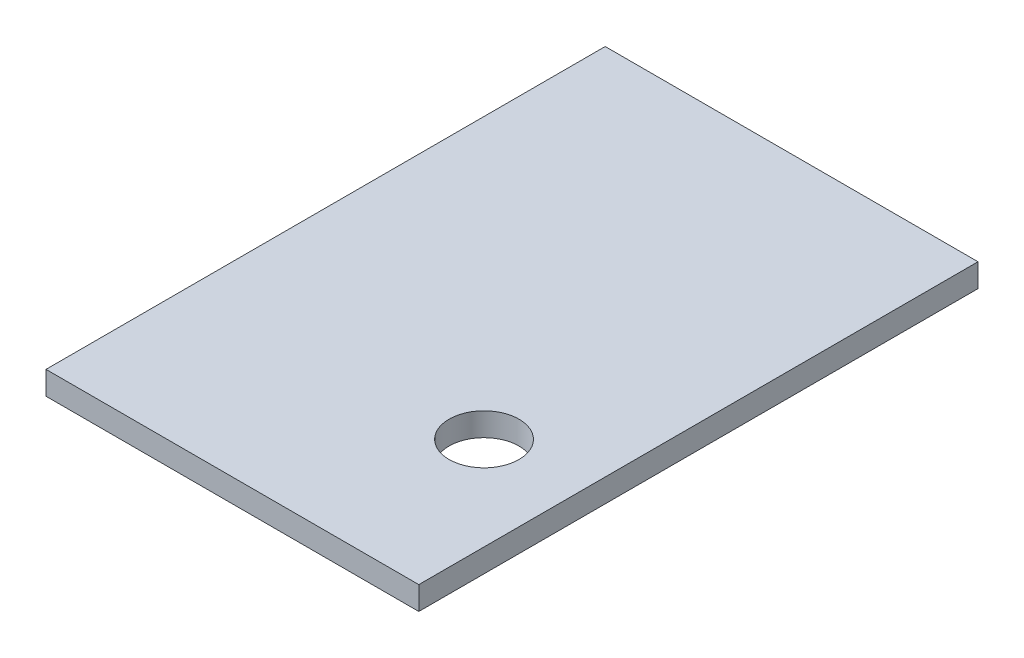
SolidWorks part; units mm, degrees
ref_plane "Front Plane" through (0, 0, 0) normal (0, 0, 1) x (1, 0, 0)
ref_plane "Top Plane" through (0, 0, 0) normal (0, 1, 0) x (1, 0, 0)
ref_plane "Right Plane" through (0, 0, 0) normal (1, 0, 0) x (0, 0, -1)
sketch "Sketch1" plane through (0, 0, 0) normal (0, 1, 0) x (1, 0, 0)
  line L1 (-25.4, 38.1) -> (25.4, 38.1)
  line L2 (-25.4, 38.1) -> (-25.4, -38.1)
  line L3 (-25.4, -38.1) -> (25.4, -38.1)
  line L4 (25.4, 38.1) -> (25.4, -38.1)
  line L5 (-25.4, 38.1) -> (25.4, -38.1) construction
  line L6 (-25.4, -38.1) -> (25.4, 38.1) construction
  point P4 (0, 0)
  dimension "D1" = 50.8
  dimension "D2" = 76.2
extrude "Boss-Extrude1" add sketch "Sketch1" along normal blind 3.175
sketch "Sketch2" plane through (0, 3.175, 0) normal (0, 1, 0) x (1, 0, 0)
  line L0 (12.7, 38.1) -> (12.7, -38.1) construction
  line L1 (25.4, 38.1) -> (-25.4, 38.1) construction
  line L2 (-25.4, -38.1) -> (25.4, -38.1) construction
  line L3 (-25.4, -16.51) -> (25.4, -16.51) construction
  line L4 (-25.4, 38.1) -> (-25.4, -38.1) construction
  line L5 (25.4, -38.1) -> (25.4, 38.1) construction
  circle A0 centre (12.7, -16.51) radius 4.7625
  dimension "D3" = 9.525
  dimension "D1" = 38.1
  dimension "D2" = 54.61
extrude "Cut-Extrude1" cut sketch "Sketch2" against normal through all
